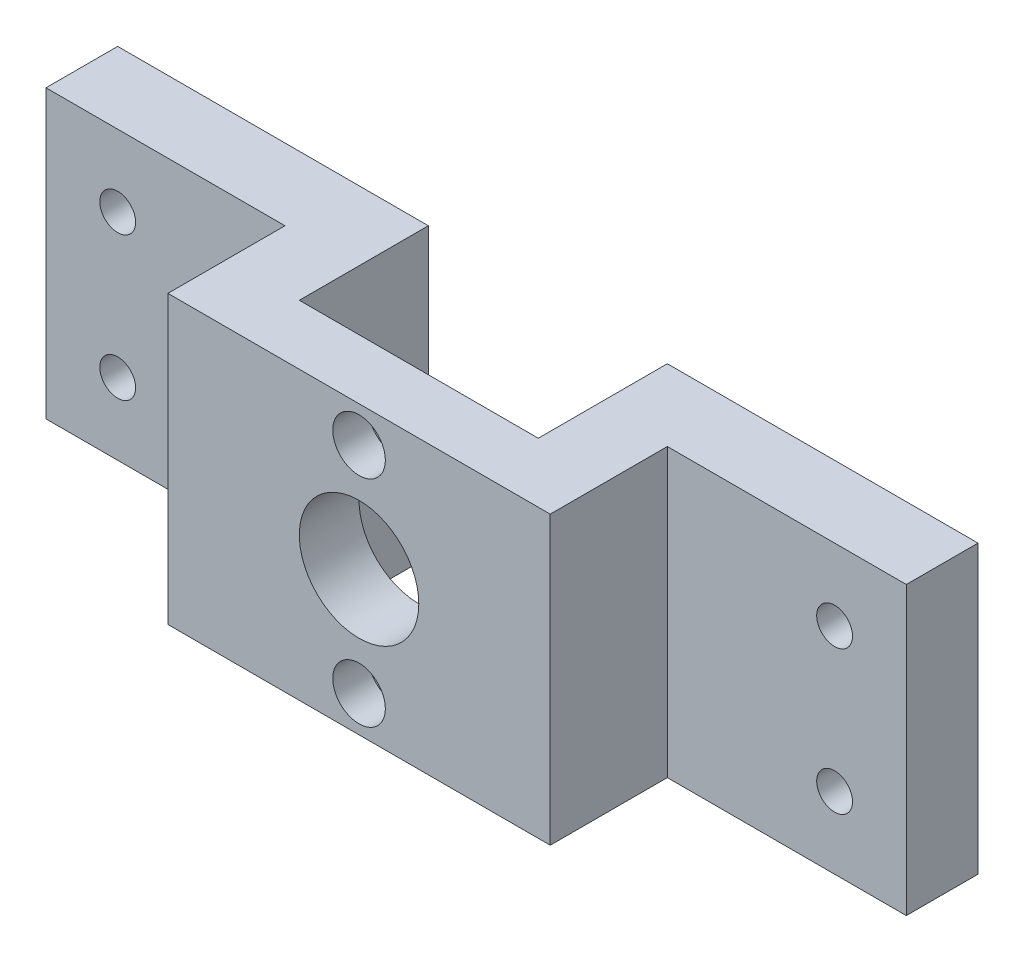
SolidWorks part; units mm, degrees
ref_plane "前视基准面" through (0, 0, 0) normal (0, 0, 1) x (1, 0, 0)
ref_plane "上视基准面" through (0, 0, 0) normal (0, 1, 0) x (1, 0, 0)
ref_plane "右视基准面" through (0, 0, 0) normal (1, 0, 0) x (0, 0, -1)
other "Configuration Table"
sketch "草图1" plane through (0, 0, 0) normal (0, 0, 1) x (1, 0, 0)
  line L0 (0, 4.5) -> (0, -4.5) construction
  line L1 (-5, -6) -> (5, -6)
  line L2 (-5, -6) -> (-5, 6)
  line L3 (-5, 6) -> (5, 6)
  line L4 (5, -6) -> (5, 6)
  line L5 (-5, -6) -> (5, 6) construction
  line L6 (-5, 6) -> (5, -6) construction
  line L9 (-5, 6) -> (-5, -6)
  circle A4 centre (0, 4.5) radius 0.85
  circle A5 centre (0, -4.5) radius 0.85
  circle A6 centre (0, 4.5) radius 1.1
  circle A7 centre (0, -4.5) radius 1.1
  circle A8 centre (0, 0) radius 2.5
  point P0 (0, 0)
  dimension "D1" = 1.7
  dimension "D2" = 1.7
  dimension "D3" = 2.2
  dimension "D5" = 5
  dimension "D4" = 9
  dimension "D6" = 10
  dimension "D7" = 12
extrude "凸台-拉伸1" add sketch "草图1" along normal mid plane 2.5 contours L2 | L4 | L2 L3 L4 L1 | A4 | A5 | A8 region at (-4.8438, 0, 0)
extrude "切除-拉伸1" cut sketch "草图1<6>" against normal offset from surface (1.5 mm away) 1 from surface contours A6 | A7 up to face at (0, 0, -1.25) starting at face at (0.85, -4.5, 1.25)
sketch "草图1<6>" plane through (0, 0, 0) normal (0, 0, 1) x (1, 0, 0) same geometry as "草图1"
sketch "草图2" plane through (0, 0, 1.25) normal (0, 0, 1) x (1, 0, 0)
  line L0 (5, -6) -> (5, 6) construction
  line L1 (5, 6) -> (8, 6)
  line L2 (5, 6) -> (5, -6)
  line L3 (5, -6) -> (8, -6)
  line L4 (8, 6) -> (8, -6)
  line L5 (-5, 6) -> (5, 6) construction
  line L6 (-5, -6) -> (-5, 6) construction
  line L7 (-5, 6) -> (-8, 6)
  line L8 (-5, 6) -> (-5, -6)
  line L9 (-5, -6) -> (-8, -6)
  line L10 (-8, 6) -> (-8, -6)
  dimension "D1" = 3
extrude "凸台-拉伸2" add sketch "草图2" against normal blind 7.9
sketch "草图3" plane through (0, 6, 0) normal (0, 1, 0) x (1, 0, 0)
  line L0 (-8, 6.65) -> (-8, -1.25) construction
  line L1 (-8, 6.65) -> (-18, 6.65)
  line L2 (-8, 6.65) -> (-8, 3.65)
  line L3 (-8, 3.65) -> (-18, 3.65)
  line L4 (-18, 6.65) -> (-18, 3.65)
  line L5 (-5, 6.65) -> (-8, 6.65) construction
  line L6 (8, 6.65) -> (5, 6.65) construction
  line L7 (8, 6.65) -> (18, 6.65)
  line L8 (8, 6.65) -> (8, 3.65)
  line L9 (8, 3.65) -> (18, 3.65)
  line L10 (18, 6.65) -> (18, 3.65)
  line L11 (8, 6.65) -> (8, -1.25) construction
  dimension "D1" = 3
  dimension "D2" = 10
extrude "凸台-拉伸3" add sketch "草图3" against normal up to surface (12 mm away) up to face at (0, -6, -3.325)
sketch "草图4" plane through (0, 0, -6.65) normal (0, 0, -1) x (-1, 0, 0)
  line L0 (18, -6) -> (18, 6) construction
  line L2 (18, -6) -> (5, -6) construction
  line L3 (-18, 6) -> (-5, 6) construction
  line L4 (-18, -6) -> (-18, 6) construction
  circle A0 centre (15, -3) radius 0.75
  circle A1 centre (15, 3) radius 0.75
  circle A2 centre (15, 3) radius 1.5
  circle A3 centre (15, -3) radius 1.5
  circle A4 centre (-15, -3) radius 0.75
  circle A5 centre (-15, 3) radius 0.75
  circle A6 centre (-15, 3) radius 1.5
  circle A7 centre (-15, -3) radius 1.5
  dimension "D1" = 1.5
  dimension "D2" = 3
  dimension "D3" = 3
  dimension "D4" = 3
  dimension "D5" = 3
  dimension "D6" = 3
extrude "切除-拉伸2" cut sketch "草图4" against normal through all contours A0 | A1 | A4 | A5
extrude "切除-拉伸3" cut sketch "草图4<3>" against normal offset from surface (1.5 mm away) 1.5 contours A2 | A3 | A7 | A6 up to face at (-14.25, 3, -3.65)
sketch "草图4<3>" plane through (0, 0, -6.65) normal (0, 0, -1) x (-1, 0, 0) same geometry as "草图4"
